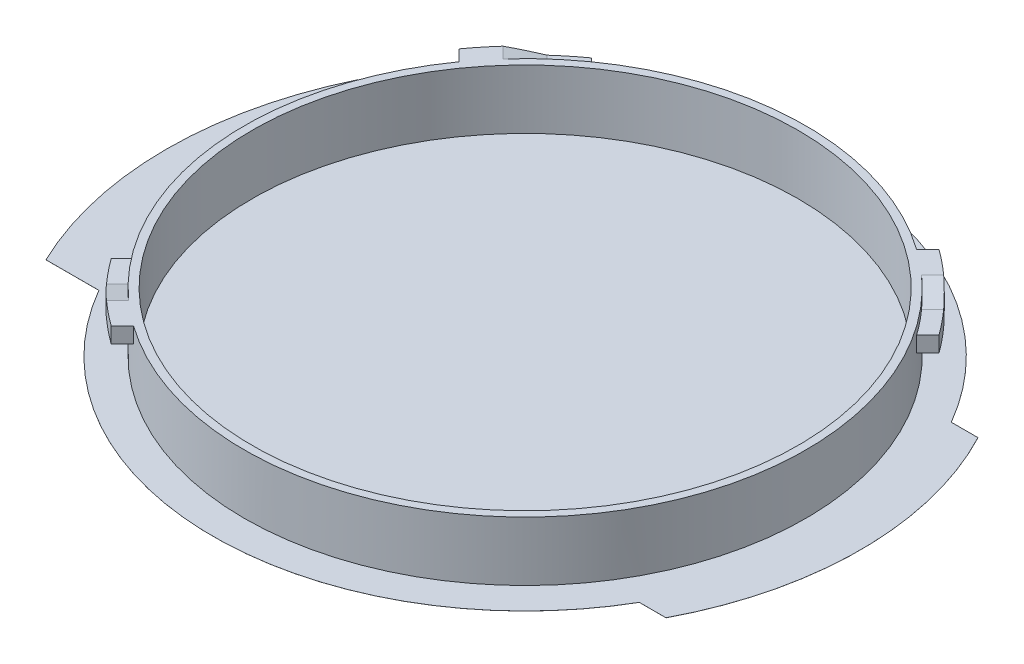
SolidWorks part; units mm, degrees
ref_plane "Płaszczyzna przednia" through (0, 0, 0) normal (0, 0, 1) x (1, 0, 0)
ref_plane "Płaszczyzna górna" through (0, 0, 0) normal (0, 1, 0) x (1, 0, 0)
ref_plane "Płaszczyzna prawa" through (0, 0, 0) normal (1, 0, 0) x (0, 0, -1)
sketch "Sketch1" plane through (0, 0, 0) normal (0, 1, 0) x (1, 0, 0)
  line L0 (-20.7123, 10) -> (-17.3205, 10)
  line L1 (-20.7123, -10) -> (-17.3205, -10)
  line L2 (17.3205, 10) -> (19.0329, 10)
  line L3 (17.3205, -10) -> (19.0329, -10)
  line L4 (0, 0) -> (-23, 0) construction
  arc A0 (17.3205, 10) -> (-17.3205, 10) centre (0, 0) ccw
  arc A1 (-20.7123, 10) -> (-20.7123, -10) centre (0, 0) ccw
  arc A3 (19.0329, -10) -> (19.0329, 10) centre (0, 0) ccw
  arc A4 (-17.3205, -10) -> (17.3205, -10) centre (0, 0) ccw
  dimension "D1" = 40
  dimension "D2" = 46
  dimension "D3" = 21.5
  dimension "D4" = 20
extrude "Boss-Extrude1" add sketch "Sketch1" along normal blind 1
sketch "Sketch2" plane through (0, 1, 0) normal (0, 1, 0) x (1, 0, 0)
  circle A0 centre (0, 0) radius 18
  circle A1 centre (0, 0) radius 17.5
  dimension "D1" = 36
  dimension "D2" = 35
extrude "Boss-Extrude2" add sketch "Sketch2" along normal blind 3.8
chamfer "Chamfer1" distance 4 angle 14 8 edges at (-19.0164, 0, -10) (-23, 0, 0) (-19.0164, 0, 10) (0, 0, 20) (18.1767, 0, 10) (21.5, 0, 0) (18.1767, 0, -10) (0, 0, -20) first distance on face at (-0.3974, 0, 0)
sketch "Sketch6" plane through (0, 1, 0) normal (0, 1, 0) x (1, 0, 0)
  line L0 (0, 0) -> (-10.6226, -10.6226) construction
  line L1 (0, 0) -> (-23, 0) construction
  dimension "D1" = 45
ref_plane "Plane3" through (-10.6226, 1, 10.6226) normal (-0.7071, 0, 0.7071) x (0.7071, 0, 0.7071)
sketch "Sketch3" plane through (0, 0, 0) normal (0, -1, 0) x (1, 0, 0)
  line L1 (-0.5, 5) -> (0.5, 5)
  line L2 (-0.5, 5) -> (-0.5, -5)
  line L3 (-0.5, -5) -> (0.5, -5)
  line L4 (0.5, 5) -> (0.5, -5)
  line L5 (-0.5, 5) -> (0.5, -5) construction
  line L6 (-0.5, -5) -> (0.5, 5) construction
  point P0 (0, 0)
  dimension "D1" = 1
  dimension "D2" = 10
extrude "Cut-Extrude1" cut sketch "Sketch3" against normal blind 0.5
ref_plane "Plane1" through (17.6616, 1, -17.6616) normal (-0.7071, 0, 0.7071) x (0.7071, 0, 0.7071)
sketch "Sketch4" plane through (17.6616, 1, -17.6616) normal (-0.7071, 0, 0.7071) x (0.7071, 0, 0.7071)
  line L0 (-3, 3.8) -> (-1, 3.8)
  line L1 (-1, 3.8) -> (1, 3.3)
  line L2 (1, 3.3) -> (3, 3.3)
  line L3 (3, 3.3) -> (3, 2.3)
  line L4 (3, 2.3) -> (1, 2.3)
  line L5 (1, 2.3) -> (-1, 2.8)
  line L6 (-1, 2.8) -> (-3, 2.8)
  line L7 (-3, 2.8) -> (-3, 3.8)
  line L8 (0, 3.55) -> (0, -1) construction
  line L9 (18, 3.8) -> (-18, 3.8) construction
  dimension "D1" = 6
  dimension "D2" = 1.5
  dimension "D3" = 2
  dimension "D4" = 2
  dimension "D5" = 2
  dimension "D6" = 2
  dimension "D7" = 1
extrude "Boss-Extrude3" add sketch "Sketch4" along normal up to next
pattern_circular "CirPattern1" count 3 every 90 about axis through (0, 4.8, 0) along (0, -1, 0) of "Boss-Extrude3" reverse direction yes
ref_plane "Plane2" through (0, 5, 0) normal (0, 1, 0) x (1, 0, 0)
sketch "Sketch5" plane through (0, 5, 0) normal (0, 1, 0) x (1, 0, 0)
  circle A0 centre (0, 0) radius 19
  circle A1 centre (0, 0) radius 34.2844
  dimension "D1" = 38
extrude "Cut-Extrude2" cut sketch "Sketch5" against normal blind 2
